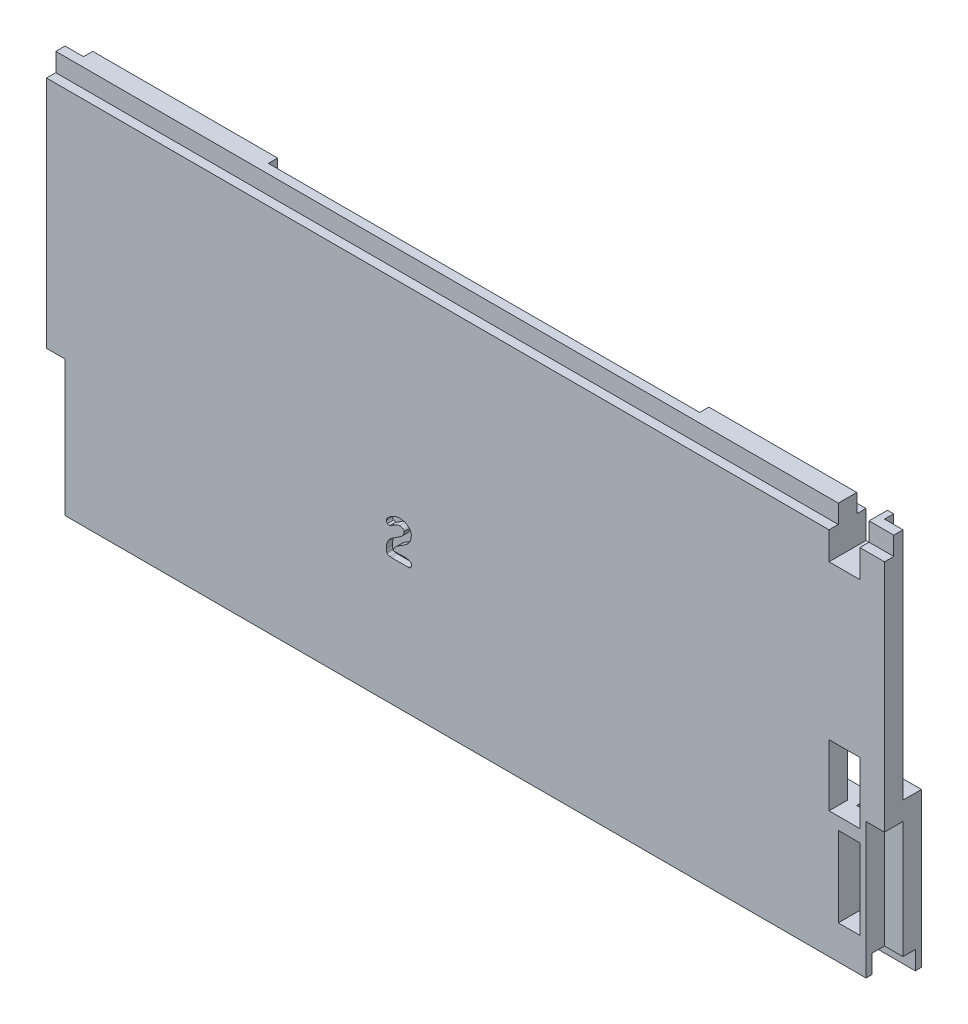
SolidWorks part; units mm, degrees
material "ABS"
ref_plane "前基準面" through (0, 0, 0) normal (0, 0, 1) x (1, 0, 0)
ref_plane "上基準面" through (0, 0, 0) normal (0, 1, 0) x (1, 0, 0)
ref_plane "右基準面" through (0, 0, 0) normal (1, 0, 0) x (0, 0, -1)
sketch "草圖1" plane through (0, 0, 0) normal (0, 0, 1) x (1, 0, 0)
  line L1 (-73.7982, 22.2202) -> (56.2018, 22.2202)
  line L2 (-73.7982, 22.2202) -> (-73.7982, -37.7798)
  line L3 (-73.7982, -37.7798) -> (56.2018, -37.7798)
  line L4 (56.2018, 22.2202) -> (56.2018, -37.7798)
  dimension "D1" = 130
  dimension "D2" = 60
extrude "填料-伸長1" add sketch "草圖1" along normal blind 6
sketch "草圖2" plane through (-73.7982, 0, 0) normal (-1, 0, 0) x (0, 0, 1)
  line L0 (6, -37.7798) -> (0, -37.7798) construction
  line L1 (0, -37.7798) -> (3, -37.7798)
  line L2 (0, -37.7798) -> (0, -12.7798)
  line L3 (0, -12.7798) -> (3, -12.7798)
  line L4 (3, -37.7798) -> (3, -12.7798)
  line L5 (6, 22.2202) -> (3, 22.2202)
  line L6 (6, 22.2202) -> (6, -15.7798)
  line L7 (6, -15.7798) -> (3, -15.7798)
  line L8 (3, 22.2202) -> (3, -15.7798)
  point P10 (4.5, -15.7798)
  line M5 (0, 22.2202) -> (0, -37.7798)
  line M6 (0, -37.7798) -> (6, -37.7798)
  dimension "D1" = 22
  dimension "D2" = 3
  dimension "D3" = 3
extrude "填料-伸長2" add sketch "草圖2" along normal blind 3 and the other way blind 133 contours L4 L3 M6 M5 | L8 L7 L6 L5 region at (-73.7982, -25.2798, 1.5)
sketch "草圖3" plane through (0, -37.7798, 0) normal (0, -1, 0) x (1, 0, 0)
  line L1 (59.2018, 1) -> (-76.7982, 1)
  line L2 (59.2018, 1) -> (59.2018, 5)
  line L3 (59.2018, 5) -> (-76.7982, 5)
  line L4 (-76.7982, 1) -> (-76.7982, 5)
  line L5 (-76.7982, 0) -> (-76.7982, 3) construction
  line L6 (-73.7982, 6) -> (56.2018, 6) construction
  dimension "D1" = 0
  dimension "D2" = 1
  dimension "D3" = 4
extrude "除料-伸長1" cut sketch "草圖3" against normal blind 3
sketch "草圖4" plane through (0, 22.2202, 0) normal (0, 1, 0) x (1, 0, 0)
  line L0 (56.2018, -3) -> (56.2018, 0) construction
  line L1 (-73.7982, -3) -> (56.2018, -3)
  line L2 (-73.7982, -3) -> (-73.7982, -1.5)
  line L3 (-73.7982, -1.5) -> (56.2018, -1.5)
  line L4 (56.2018, -3) -> (56.2018, -1.5)
  line L5 (59.2018, -6) -> (59.2018, -3) construction
  line L6 (59.2018, -4.5) -> (-76.7982, -4.5)
  line L7 (59.2018, -4.5) -> (59.2018, -3)
  line L8 (59.2018, -3) -> (-76.7982, -3)
  line L9 (-76.7982, -4.5) -> (-76.7982, -3)
  line M4 (59.2018, -6) -> (59.2018, -3)
  line M5 (59.2018, -3) -> (56.2018, -3)
  line M6 (56.2018, -3) -> (56.2018, 0)
  line M8 (-73.7982, 0) -> (-73.7982, -3)
  line M9 (-73.7982, -3) -> (-76.7982, -3)
  line M10 (-76.7982, -3) -> (-76.7982, -6)
extrude "填料-伸長3" add sketch "草圖4" along normal blind 3 contours L3 L1 M8 M6 | L6 L1 M4 M5 M9 M10 region at (-8.7982, 22.2202, 2.25) region at (-8.7982, 22.2202, 3.75)
sketch "草圖5" plane through (0, 0, 0) normal (0, 0, -1) x (-1, 0, 0)
  line L1 (-26.2018, 28.1622) -> (43.7982, 28.1622)
  line L2 (-26.2018, 28.1622) -> (-26.2018, -21.2951)
  line L3 (-26.2018, -21.2951) -> (43.7982, -21.2951)
  line L4 (43.7982, 28.1622) -> (43.7982, -21.2951)
  line L6 (-59.2018, -12.7798) -> (-59.2018, -37.7798) construction
  line L7 (76.7982, -12.7798) -> (76.7982, -37.7798) construction
  dimension "D1" = 33
  dimension "D2" = 33
extrude "除料-伸長2" cut sketch "草圖5" against normal blind 3
sketch "草圖6" plane through (0, 0, 6) normal (0, 0, 1) x (1, 0, 0)
  line L0 (56.2018, -37.7798) -> (56.2018, -15.7798) construction
  line L1 (55.2018, -32.2798) -> (51.7018, -32.2798)
  line L2 (55.2018, -32.2798) -> (55.2018, -19.2798)
  line L3 (55.2018, -19.2798) -> (51.7018, -19.2798)
  line L4 (51.7018, -32.2798) -> (51.7018, -19.2798)
  line L5 (-73.7982, -37.7798) -> (56.2018, -37.7798) construction
  line L7 (55.2018, -17.2798) -> (50.2018, -17.2798)
  line L8 (55.2018, -17.2798) -> (55.2018, -7.2798)
  line L9 (55.2018, -7.2798) -> (50.2018, -7.2798)
  line L10 (50.2018, -17.2798) -> (50.2018, -7.2798)
  line L11 (55.2018, 17.7202) -> (50.2018, 17.7202)
  line L12 (55.2018, 17.7202) -> (55.2018, 33.7202)
  line L13 (55.2018, 33.7202) -> (50.2018, 33.7202)
  line L14 (50.2018, 17.7202) -> (50.2018, 33.7202)
  dimension "D1" = 1
  dimension "D2" = 5.5
  dimension "D3" = 13
  dimension "D4" = 3.5
  dimension "D5" = 20.5
  dimension "D6" = 10
  dimension "D7" = 5
  dimension "D8" = 55.5
  dimension "D9" = 16
  dimension "D10" = 5
extrude "除料-伸長3" cut sketch "草圖6" against normal blind 65
sketch "草圖7" plane through (0, 0, 0) normal (0, 0, -1) x (-1, 0, 0)
  line L0 (-26.2018, 22.2202) -> (-26.2018, -21.2951) construction
  line L1 (-51.7018, -7.2798) -> (-26.2018, -7.2798)
  line L2 (-51.7018, -7.2798) -> (-51.7018, -17.2798)
  line L3 (-51.7018, -17.2798) -> (-26.2018, -17.2798)
  line L4 (-26.2018, -7.2798) -> (-26.2018, -17.2798)
  line L6 (-55.2018, -17.2798) -> (-51.7018, -17.2798)
  line L7 (-55.2018, -17.2798) -> (-55.2018, -19.2798)
  line L8 (-55.2018, -19.2798) -> (-51.7018, -19.2798)
  line L9 (-51.7018, -17.2798) -> (-51.7018, -19.2798)
  point P10 (0, 0)
  line M3 (-55.2018, -19.2798) -> (-51.7018, -19.2798)
  line M5 (-50.2018, -17.2798) -> (-55.2018, -17.2798)
  line M8 (-50.2018, -7.2798) -> (-50.2018, -17.2798)
  line M16 (-26.2018, -21.2951) -> (-26.2018, 22.2202)
extrude "除料-伸長4" cut sketch "草圖7" against normal blind 3 contours L3 L1 M8 M16 | L9 L7 M5 M3 region at (53.4518, -18.2798, 0) region at (38.2018, -12.2798, 0)
sketch "草圖8" plane through (0, 0, 6) normal (0, 0, 1) x (1, 0, 0)
  text T0 "2" font "Comic Sans MS" height in points 22
extrude "除料-伸長5" cut sketch "草圖8" against normal blind 1
chamfer "導角1" distance 10 distance2 3 1 edges at (-8.7982, -21.2951, 0) first distance on face at (16.8836, -5.1903, 0)
